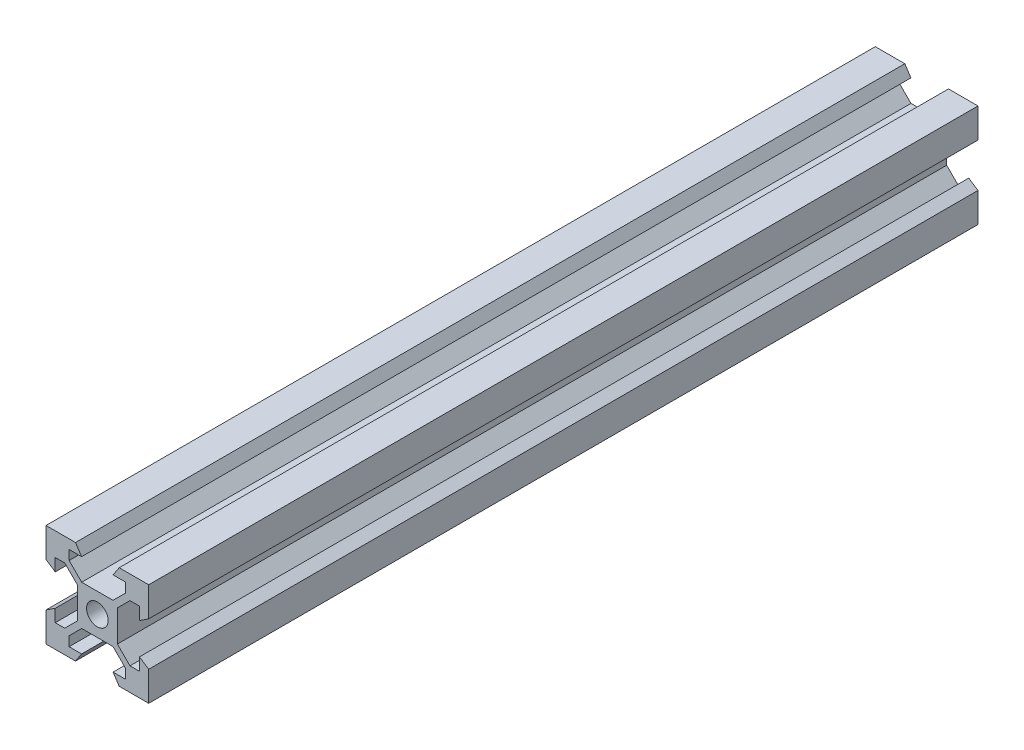
SolidWorks part; units mm, degrees
ref_plane "Front Plane" through (0, 0, 0) normal (0, 0, 1) x (1, 0, 0)
ref_plane "Top Plane" through (0, 0, 0) normal (0, 1, 0) x (1, 0, 0)
ref_plane "Right Plane" through (0, 0, 0) normal (1, 0, 0) x (0, 0, -1)
sketch "Sketch1" plane through (0, 0, 0) normal (0, 0, 1) x (1, 0, 0)
  line L0 (-10, 10) -> (-4.25, 10)
  line L1 (-4.25, 10) -> (-3.065, 8.2)
  line L2 (-3.065, 8.2) -> (-5.5, 8.2)
  line L3 (-5.5, 8.2) -> (-5.5, 6.3485)
  line L4 (-5.5, 6.3485) -> (-3.0515, 3.9)
  line L5 (-3.0515, 3.9) -> (0, 3.9)
  line L6 (-10, 10) -> (0, 0) construction
  line L7 (-3.9, 3.0515) -> (-3.9, 0)
  line L8 (-6.3485, 5.5) -> (-3.9, 3.0515)
  line L9 (-8.2, 3.065) -> (-8.2, 5.5)
  line L10 (-8.2, 5.5) -> (-6.3485, 5.5)
  line L11 (-10, 4.25) -> (-8.2, 3.065)
  line L12 (-10, 10) -> (-10, 4.25)
  line L13 (10, 10) -> (10, 4.25)
  line L14 (10, 10) -> (4.25, 10)
  line L15 (4.25, 10) -> (3.065, 8.2)
  line L16 (3.065, 8.2) -> (5.5, 8.2)
  line L17 (5.5, 8.2) -> (5.5, 6.3485)
  line L18 (8.2, 5.5) -> (6.3485, 5.5)
  line L19 (8.2, 3.065) -> (8.2, 5.5)
  line L20 (10, 4.25) -> (8.2, 3.065)
  line L21 (3.9, 3.0515) -> (3.9, 0)
  line L22 (6.3485, 5.5) -> (3.9, 3.0515)
  line L23 (5.5, 6.3485) -> (3.0515, 3.9)
  line L24 (3.0515, 3.9) -> (0, 3.9)
  line L25 (10, -10) -> (4.25, -10)
  line L26 (10, -10) -> (10, -4.25)
  line L27 (10, -4.25) -> (8.2, -3.065)
  line L28 (8.2, -3.065) -> (8.2, -5.5)
  line L29 (8.2, -5.5) -> (6.3485, -5.5)
  line L30 (5.5, -8.2) -> (5.5, -6.3485)
  line L31 (3.065, -8.2) -> (5.5, -8.2)
  line L32 (4.25, -10) -> (3.065, -8.2)
  line L33 (3.0515, -3.9) -> (0, -3.9)
  line L34 (5.5, -6.3485) -> (3.0515, -3.9)
  line L35 (6.3485, -5.5) -> (3.9, -3.0515)
  line L36 (3.9, -3.0515) -> (3.9, 0)
  line L37 (-10, -10) -> (-10, -4.25)
  line L38 (-10, -10) -> (-4.25, -10)
  line L39 (-4.25, -10) -> (-3.065, -8.2)
  line L40 (-3.065, -8.2) -> (-5.5, -8.2)
  line L41 (-5.5, -8.2) -> (-5.5, -6.3485)
  line L42 (-8.2, -5.5) -> (-6.3485, -5.5)
  line L43 (-8.2, -3.065) -> (-8.2, -5.5)
  line L44 (-10, -4.25) -> (-8.2, -3.065)
  line L45 (-3.9, -3.0515) -> (-3.9, 0)
  line L46 (-6.3485, -5.5) -> (-3.9, -3.0515)
  line L47 (-5.5, -6.3485) -> (-3.0515, -3.9)
  line L48 (-3.0515, -3.9) -> (0, -3.9)
  circle A0 centre (0, 0) radius 2.1
  point P58 (0, 0)
  dimension "D1" = 4.2
  dimension "D2" = 10
  dimension "D3" = 10
  dimension "D4" = 6.1
  dimension "D5" = 4.3
  dimension "D6" = 3.065
  dimension "D7" = 5.5
  dimension "D8" = 1.2
  dimension "D9" = 4.25
  dimension "D10" = 4
extrude "Boss-Extrude1" add sketch "Sketch1" along normal blind 161.5
